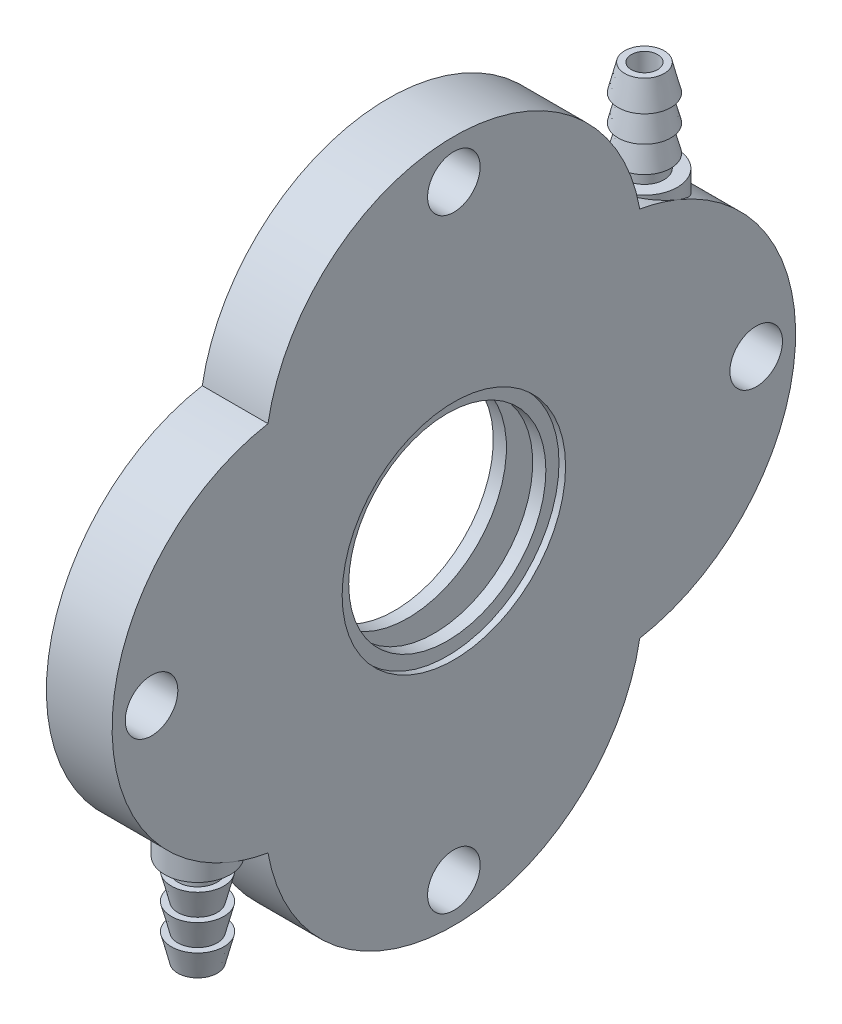
SolidWorks part; units mm, degrees
ref_plane "Front Plane" through (0, 0, 0) normal (0, 0, 1) x (1, 0, 0)
ref_plane "Top Plane" through (0, 0, 0) normal (0, 1, 0) x (1, 0, 0)
ref_plane "Right Plane" through (0, 0, 0) normal (1, 0, 0) x (0, 0, -1)
sketch "Sketch2" plane through (0, 0, 0) normal (1, 0, 0) x (0, 0, -1)
  line L1 (-14.1421, -14.1421) -> (14.1421, -14.1421) construction
  line L2 (-14.1421, -14.1421) -> (-14.1421, 14.1421) construction
  line L3 (-14.1421, 14.1421) -> (14.1421, 14.1421) construction
  line L4 (14.1421, -14.1421) -> (14.1421, 14.1421) construction
  circle A1 centre (0, 23) radius 2
  circle A2 centre (23, 0) radius 2
  circle A3 centre (0, -23) radius 2
  circle A4 centre (-23, 0) radius 2
  circle A5 centre (0, 0) radius 7.5
  circle A6 centre (0, 0) radius 8.5 construction
  circle A10 centre (0, 0) radius 18 construction
  circle A11 centre (0, 0) radius 26 construction
  circle A12 centre (0, -23) radius 3 construction
  circle A14 centre (23, 0) radius 3 construction
  arc A25 (-14.1421, 14.1421) -> (-14.1421, -14.1421) centre (-11.6378, 0) ccw
  arc A26 (-14.1421, -14.1421) -> (14.1421, -14.1421) centre (0, -11.6378) ccw
  circle A27 centre (0, 0) radius 20 construction
  arc A28 (14.1421, 14.1421) -> (-14.1421, 14.1421) centre (0, 11.6378) ccw
  arc A29 (14.1421, -14.1421) -> (14.1421, 14.1421) centre (11.6378, 0) ccw
  point P14 (0, 0)
  point P36 (0, 0)
  point P49 (0, 0)
  dimension "D1" = 36
  dimension "D3" = 4
  dimension "D5" = 15
  dimension "D6" = 17
  dimension "D7" = 52
  dimension "D8" = 40
  dimension "D4" = 23
  dimension "D2" = 4
  dimension "D9" = 4
extrude "Body" add sketch "Sketch2" along normal mid plane 5
sketch "Sketch3" plane through (2.5, 0, 0) normal (1, 0, 0) x (0, 0, -1)
  circle A0 centre (0, 0) radius 8.5
  dimension "D1" = 17
extrude "O-Ring Seat" cut sketch "Sketch3" against normal blind 0.5
mirror "Mirror1" about plane through (0, 0, 0) normal (1, 0, 0) of "O-Ring Seat"
sketch "Sketch8" plane through (0, 0, 0) normal (-1, 0, 0) x (0, 0, 1)
  circle A0 centre (0, 0) radius 18
  dimension "D1" = 36
extrude "Cavity" cut sketch "Sketch8" against normal mid plane 2
sketch "Sketch5" plane through (0, 0, 0) normal (0, 1, 0) x (1, 0, 0)
  line L1 (0, -28.6) -> (0, 28.6) construction
  circle A0 centre (0, 17) radius 1
  dimension "D1" = 2
  dimension "D2" = 17
extrude "Outlet" cut sketch "Sketch5" along normal through all
ref_plane "Plane2" through (0, 14.1421, 0) normal (0, 1, 0) x (1, 0, 0)
sketch "Sketch6" plane through (0, 14.1421, 0) normal (0, 1, 0) x (1, 0, 0)
  circle A2 centre (0, 17) radius 1
  circle A3 centre (0, 17) radius 2.5
  dimension "D1" = 5
extrude "Boss-Extrude2" add sketch "Sketch6" against normal up to next
ref_axis "Axis1" through (0, 13.7536, -17) along (0, -1, 0)
sketch "Sketch9" plane through (0, 0, 0) normal (1, 0, 0) x (0, 0, -1)
  line L0 (18, 14.1421) -> (18, 21.1421)
  line L1 (18, 21.1421) -> (18.5, 21.1421)
  line L2 (18.5, 21.1421) -> (19, 19.1421)
  line L3 (19, 19.1421) -> (18.5, 19.1421)
  line L4 (18.5, 19.1421) -> (19, 17.1421)
  line L5 (19, 17.1421) -> (18.5, 17.1421)
  line L6 (18.5, 17.1421) -> (19, 15.1421)
  line L7 (19, 15.1421) -> (18.5, 15.1421)
  line L8 (18.5, 15.1421) -> (18.5, 14.1421)
  line L9 (18.5, 14.1421) -> (18, 14.1421)
  line L10 (17, 13.7536) -> (17, 0) construction
  line L11 (19.5, 14.1421) -> (14.5, 14.1421) construction
  dimension "D1" = 0.5
  dimension "D2" = 0.5
  dimension "D3" = 2
  dimension "D4" = 1
  dimension "D5" = 1
revolve "Revolve1" add sketch "Sketch9" angle 360 about axis through (0, 13.7536, -17) along (0, -1, 0)
pattern_circular "Inlet" count 2 every 180 about axis through (2, 0, 0) along (1, 0, 0) of "Boss-Extrude2", "Revolve1", "Outlet"
